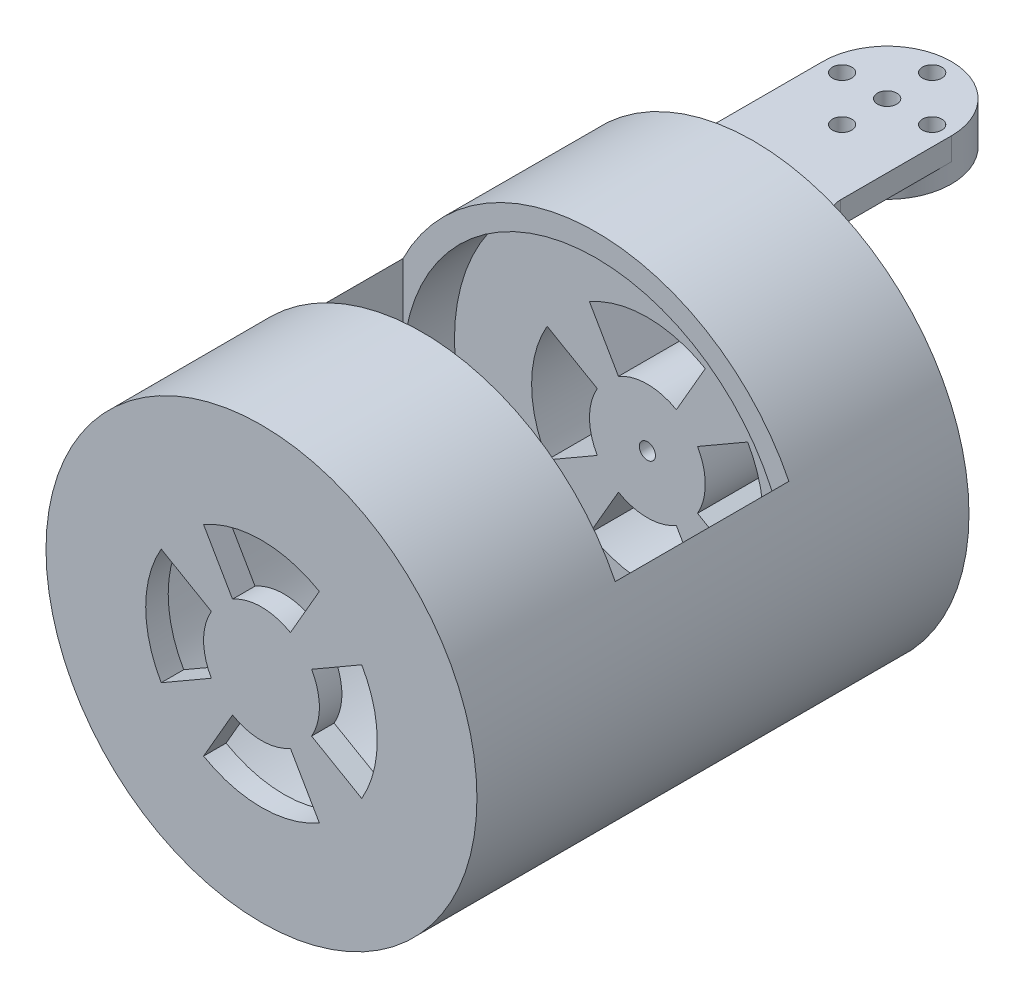
SolidWorks part; units mm, degrees
ref_plane "Front Plane" through (0, 0, 0) normal (0, 0, 1) x (1, 0, 0)
ref_plane "Top Plane" through (0, 0, 0) normal (0, 1, 0) x (1, 0, 0)
ref_plane "Right Plane" through (0, 0, 0) normal (1, 0, 0) x (0, 0, -1)
sketch "Sketch1" plane through (0, 0, 0) normal (0, 0, 1) x (1, 0, 0)
  circle A0 centre (0, 0) radius 30
  circle A1 centre (0, 0) radius 33.5
extrude "Boss-Extrude1" add sketch "Sketch1" along normal blind 76.5
sketch "Sketch3" plane through (0, 0, 0) normal (0, 0, -1) x (-1, 0, 0)
  circle A0 centre (0, 0) radius 33.5
extrude "Boss-Extrude2" add sketch "Sketch3" against normal blind 16.5
sketch "Sketch4" plane through (0, 0, 0) normal (0, 0, -1) x (-1, 0, 0)
  line L0 (0, 0) -> (15.5885, 9)
  line L1 (-10, 28.8) -> (10, 28.8)
  line L2 (-10, 28.8) -> (-10, 25.3)
  line L3 (-10, 25.3) -> (10, 25.3)
  line L4 (10, 28.8) -> (10, 25.3)
  line L5 (-5.5, -25.5) -> (5.5, -25.5)
  line L6 (-5.5, -25.5) -> (-5.5, -29)
  line L7 (-5.5, -29) -> (5.5, -29)
  line L8 (5.5, -25.5) -> (5.5, -29)
  line L9 (0, 0) -> (15.5885, -9)
  line L10 (0, 0) -> (18, 0) construction
  circle A0 centre (0, 0) radius 1.25
  circle A1 centre (0, 0) radius 9
  circle A2 centre (0, 0) radius 18
  dimension "D5" = 60
  dimension "D1" = 5.5
  dimension "D2" = 10
  dimension "D3" = 25.3
  dimension "D4" = 25.5
  dimension "D6" = 30
extrude "Boss-Extrude4" add sketch "Sketch4" along normal blind 30.867 contours L3 L4 L1 L2
extrude "Boss-Extrude5" add sketch "Sketch4<5>" along normal blind 27 contours L7 L8 L5 L6
sketch "Sketch4<5>" plane through (0, 0, 0) normal (0, 0, -1) x (-1, 0, 0) same geometry as "Sketch4"
extrude "Cut-Extrude1" cut sketch "Sketch4<7>" against normal through all contours A0
sketch "Sketch4<7>" plane through (0, 0, 0) normal (0, 0, -1) x (-1, 0, 0) same geometry as "Sketch4"
fillet "Fillet1" radius 3.5 2 edges at (10, 27.05, 0) (-10, 27.05, 0)
fillet "Fillet2" radius 1.5 2 edges at (5.5, -27.25, 0) (-5.5, -27.25, 0)
sketch "Sketch6" plane through (0, 25.3, 0) normal (0, -1, 0) x (1, 0, 0)
  line L0 (10, -20.7738) -> (10, -30.867)
  line L1 (10, -30.867) -> (-10, -30.867)
  line L2 (-10, -30.867) -> (-10, -20.7738)
  line L3 (-10, -20.7738) -> (10, -20.7738)
  circle A0 centre (0, -20.7738) radius 10
  line M4 (-10, -3.5) -> (-10, -30.867)
  line M5 (-10, -30.867) -> (10, -30.867)
  line M6 (10, -30.867) -> (10, -3.5)
extrude "Cut-Extrude4" cut sketch "Sketch6" against normal through all contours A0 M4 M5 M6 region at (9.776, 25.3, -25.8204)
extrude "Boss-Extrude7" add sketch "Sketch6<10>" along normal blind 3 contours A0
sketch "Sketch6<10>" plane through (0, 25.3, 0) normal (0, -1, 0) x (1, 0, 0) same geometry as "Sketch6"
sketch "Sketch12" plane through (0, 22.3, 0) normal (0, -1, 0) x (1, 0, 0)
  line L0 (0, -20.7738) -> (-7, -20.7738) construction
  circle A0 centre (0, -20.7738) radius 5
  circle A1 centre (0, -20.7738) radius 3
  circle A2 centre (-7, -20.7738) radius 1.5
  circle A3 centre (0, -20.7738) radius 1.5
  dimension "D1" = 7
extrude "Boss-Extrude8" add sketch "Sketch12" along normal blind 1.5 contours A1 A0 region at (-4.8586, 22.3, -20.7738)
extrude "Cut-Extrude7" cut sketch "Sketch12<3>" against normal through all contours A2
sketch "Sketch12<3>" plane through (0, 22.3, 0) normal (0, -1, 0) x (1, 0, 0) same geometry as "Sketch12"
pattern_circular "CirPattern1" count 4 every 90 about axis through (0, 20.8, -20.7738) along (0, -1, 0) of "Cut-Extrude7"
extrude "Cut-Extrude8" cut sketch "Sketch12<4>" against normal through all contours A3
sketch "Sketch12<4>" plane through (0, 22.3, 0) normal (0, -1, 0) x (1, 0, 0) same geometry as "Sketch12"
extrude "Cut-Extrude9" cut sketch "Sketch4<8>" against normal through all contours A1 L10 A2 L0 | L10 A1 L9 A2 region at (-13.369, 3.5822, 0) region at (-13.369, -3.5822, 0)
sketch "Sketch4<8>" plane through (0, 0, 0) normal (0, 0, -1) x (-1, 0, 0) same geometry as "Sketch4"
pattern_circular "CirPattern2" count 4 every 90 about axis through (0, 0, 0) along (0, 0, -1) of "Cut-Extrude9"
ref_plane "Plane3" through (0, 33.5, 0) normal (0, 1, 0) x (1, 0, 0)
sketch "Sketch13" plane through (0, 33.5, 0) normal (0, 1, 0) x (1, 0, 0)
  line L0 (0, -76.5) -> (0, -104.9565) construction
  line L1 (-30, -51.5) -> (30, -51.5)
  line L2 (-30, -51.5) -> (-30, -24.5)
  line L3 (-30, -24.5) -> (30, -24.5)
  line L4 (30, -51.5) -> (30, -24.5)
  line L5 (-33.5, -76.5) -> (33.5, -76.5) construction
  dimension "D1" = 60
  dimension "D2" = 30
  dimension "D3" = 25
extrude "Cut-Extrude11" cut sketch "Sketch13" against normal blind 33.5 contours L3 L4 L1 L2
sketch "Sketch14" plane through (0, 0, 76.5) normal (0, 0, 1) x (1, 0, 0)
  line L0 (0, 0) -> (15.5885, 9)
  line L1 (0, 0) -> (15.5885, -9)
  line L2 (0, 0) -> (18, 0) construction
  circle A0 centre (0, 0) radius 33.5
  circle A1 centre (0, 0) radius 18
  circle A2 centre (0, 0) radius 9
  dimension "D1" = 60
  dimension "D2" = 30
extrude "Boss-Extrude9" add sketch "Sketch14" against normal blind 3.5 contours A0
extrude "Cut-Extrude12" cut sketch "Sketch14<3>" against normal blind 4 contours A2 L2 A1 L0 | L2 A2 L1 A1 region at (13.369, 3.5822, 76.5) region at (13.369, -3.5822, 76.5)
sketch "Sketch14<3>" plane through (0, 0, 76.5) normal (0, 0, 1) x (1, 0, 0) same geometry as "Sketch14"
pattern_circular "CirPattern3" count 4 over 360 about axis through (0, 0, 16.5) along (0, 0, -1) of "Cut-Extrude12"
ref_plane "Plane4" through (0, 0, 0) normal (0, 1, 0) x (1, 0, 0)
sketch "Sketch15" plane through (0, 0, 0) normal (0, 1, 0) x (1, 0, 0)
  line L0 (0, 20.7738) -> (-1.5, 20.7738) construction
  line L1 (-1.5, 20.7738) -> (0, 20.7738) construction
  line L2 (0, 20.7738) -> (0, 22.2738) construction
  circle A0 centre (0, 20.7738) radius 1.5
sketch "Sketch16" plane through (0, -29, 0) normal (0, -1, 0) x (1, 0, 0)
  circle A0 centre (0, -20.7738) radius 2.7
  circle A1 centre (0, -20.7738) radius 5.5
  point P4 (0, 0)
  point P5 (0, 0)
  line M3 (-5.5, -1.5) -> (-5.5, -27)
  line M4 (-5.5, -27) -> (5.5, -27)
  line M5 (5.5, -27) -> (5.5, -1.5)
extrude "Cut-Extrude13" cut sketch "Sketch16" against normal blind 10 contours A1 M3 M4 M5 | A0 region at (0, -29, -20.7738) region at (5.3736, -29, -23.8869)
